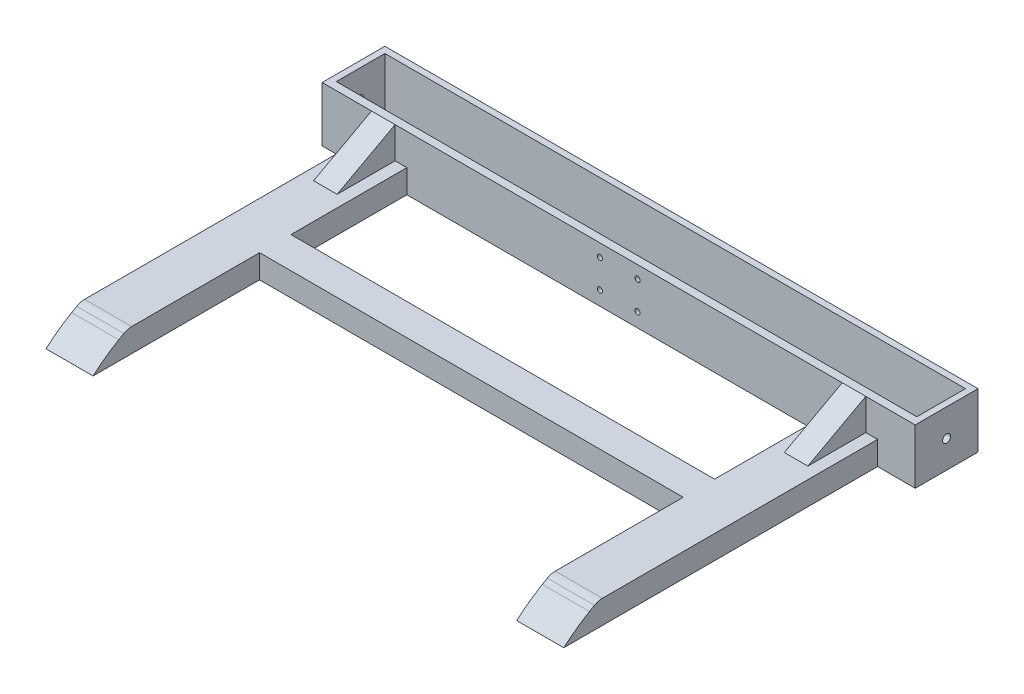
SolidWorks part; units mm, degrees
ref_plane "前视基准面" through (0, 0, 0) normal (0, 0, 1) x (1, 0, 0)
ref_plane "上视基准面" through (0, 0, 0) normal (0, 1, 0) x (1, 0, 0)
ref_plane "右视基准面" through (0, 0, 0) normal (1, 0, 0) x (0, 0, -1)
other "Configuration Table"
sketch "草图1" plane through (0, 0, 0) normal (0, 0, 1) x (1, 0, 0)
  line L0 (0, 0) -> (100.5587, 0) construction
  line L1 (0, 0) -> (0, 57.8212) construction
  line L2 (-189, 0) -> (189, 0)
  line L3 (-189, 0) -> (-189, 35)
  line L4 (189, 0) -> (189, 35)
  line L5 (189, 35) -> (-189, 35)
  point P8 (0, 0)
  dimension "D1" = 35
  dimension "D2" = 378
extrude "凸台-拉伸1" add sketch "草图1" along normal mid plane 5
sketch "草图2" plane through (0, 0, 2.5) normal (0, 0, 1) x (1, 0, 0)
  line L0 (0, 0) -> (0, 77.459) construction
  line L1 (0, 0) -> (206.4807, 0) construction
  line L2 (-12, 27) -> (-12, 9) construction
  circle A0 centre (-12, 9) radius 2
  circle A1 centre (-12, 27) radius 2
  circle A2 centre (12, 9) radius 2
  circle A3 centre (12, 27) radius 2
  point P4 (-12, 9)
  point P7 (-12, 27)
  point P9 (12, 9)
  point P11 (12, 27)
  dimension "D3" = 4
  dimension "D1" = 18
  dimension "D2" = 12
  dimension "D4" = 9
sketch "草图3" plane through (0, 0, -2.5) normal (0, 0, -1) x (-1, 0, 0)
  line L0 (0, 0) -> (0, 97.3013) construction
  line L1 (0, 0) -> (194.0159, 0) construction
  line L2 (-185, 0) -> (-185, 35)
  line L3 (-189, 35) -> (189, 35) construction
  line L4 (-189, 0) -> (-189, 35) construction
  line L5 (-189, 0) -> (-189, 35)
  line L6 (-189, 35) -> (-185, 35)
  line L8 (-189, 0) -> (-185, 0)
  line L9 (189, 0) -> (185, 0)
  line L10 (189, 35) -> (185, 35)
  line L11 (189, 0) -> (189, 35)
  line L12 (185, 0) -> (185, 35)
  dimension "D1" = 4
extrude "凸台-拉伸2" add sketch "草图3" along normal blind 35
sketch "草图4" plane through (189, 0, 0) normal (1, 0, 0) x (0, 0, -1)
  line L0 (-5, 17.5) -> (35, 17.5) construction
  line L3 (17.5, 17.5) -> (17.5, 35) construction
  line L5 (-2.5, 0) -> (37.5, 0) construction
  line L8 (-2.5, -200000) -> (-2.5, 200077.459) construction
  circle A0 centre (17.5, 17.5) radius 2.55
  point P3 (17.5, 0)
  dimension "D1" = 5.1
  dimension "D2" = 20
extrude "切除-拉伸3" cut sketch "草图4" against normal through all
hole_wizard "M4 螺纹孔的螺纹孔钻头6" positions "草图2" profile "草图5" hole size "M4" standard "GB" end condition up to next
sketch "草图5" plane through (12, 27, 2.5) normal (1, 0, 0) x (0, -1, 0)
  line L0 (0, 0) -> (0, 5)
  line L1 (0, 5) -> (1.65, 5)
  line L2 (1.65, 5) -> (1.65, 0)
  line L5 (1.65, 0) -> (0, 0)
  line L11 (0, -6.35) -> (0, 107.95) construction
  dimension "通孔孔直径" = 3.3
  dimension "通孔孔深度" = 5
sketch "草图6" plane through (0, 0, 2.5) normal (0, 0, 1) x (1, 0, 0)
  line L0 (0, 0) -> (0, 81.9275) construction
  line L2 (0, 0) -> (221.9261, 0) construction
  line L3 (-135, 15) -> (-135, 0)
  line L4 (135, 15) -> (165, 15)
  line L5 (135, 15) -> (135, 0)
  line L6 (135, 0) -> (165, 0)
  line L7 (165, 15) -> (165, 0)
  line L8 (135, 15) -> (165, 0) construction
  line L9 (135, 0) -> (165, 15) construction
  line L10 (-135, 15) -> (-165, 15)
  line L11 (-135, 0) -> (-165, 0)
  line L12 (-165, 15) -> (-165, 0)
  point P2 (150, 7.5)
  dimension "D1" = 30
  dimension "D2" = 15
  dimension "D3" = 7.5
  dimension "D4" = 150
extrude "凸台-拉伸3" add sketch "草图6" along normal blind 200
sketch "草图15" plane through (-135, 0, 0) normal (1, 0, 0) x (0, 0, -1)
  line L0 (-224.1671, 10) -> (50.3788, 10) construction
  line L2 (-86.3824, 25) -> (-86.3824, -41.1178) construction
  line L4 (-96.3824, 15) -> (-76.3824, 15)
  line L5 (-96.3824, 15) -> (-96.3824, 0)
  line L6 (-76.3824, 15) -> (-76.3824, 0)
  line L7 (-96.3824, 0) -> (-76.3824, 0)
  line L9 (-202.5, 15) -> (-2.5, 15) construction
  point P10 (-86.3824, 15)
  dimension "D1" = 15
  dimension "D2" = 20
extrude "凸台-拉伸4" add sketch "草图15" along normal up to next
sketch "草图17" plane through (185, 0, 0) normal (-1, 0, 0) x (0, 0, 1)
  line L0 (-33.5, 0) -> (-33.5, 35)
  line L1 (-37.5, 0) -> (-2.5, 0) construction
  line L2 (-37.5, 35) -> (-2.5, 35) construction
  line L3 (-37.5, 35) -> (-33.5, 35)
  line L4 (-37.5, 0) -> (-33.5, 0)
  line L5 (-37.5, 0) -> (-37.5, 35)
  dimension "D1" = 4
extrude "凸台-拉伸5" add sketch "草图17" along normal up to next
sketch "草图18" plane through (-185, 0, 0) normal (1, 0, 0) x (0, 0, -1)
  line L0 (33.5, 0) -> (33.5, 35)
  line L1 (-2.5, 0) -> (37.5, 0) construction
  line L2 (-2.5, 35) -> (37.5, 35) construction
  line L3 (33.5, 35) -> (37.5, 35)
  line L4 (37.5, 35) -> (37.5, 0)
  line L5 (37.5, 0) -> (33.5, 0)
  dimension "D1" = 4
extrude "凸台-拉伸6" add sketch "草图18" along normal blind 185
sketch "草图19" plane through (-165, 0, 0) normal (-1, 0, 0) x (0, 0, 1)
  line L0 (180.5936, 15) -> (202.5, 2.3523)
  line L1 (202.5, 15) -> (2.5, 15) construction
  line L2 (202.5, 15) -> (202.5, 0) construction
  line L3 (202.5, 2.3523) -> (158.0045, 2.3523) construction
  dimension "D1" = 30
extrude "切除-拉伸4" cut sketch "草图19" against normal through all and the other way through all
fillet "圆角1" radius 100 2 edges at (-150, 2.3523, 202.5) (150, 2.3523, 202.5)
fillet "圆角2" radius 10 2 edges at (-150, 15, 180.5936) (150, 15, 180.5936)
ref_plane "基准面1" through (150, 0, 0) normal (1, 0, 0) x (0, 0, -1)
sketch "草图20" plane through (150, 0, 0) normal (1, 0, 0) x (0, 0, -1)
  line L0 (-2.5, 35) -> (-39.4412, 15)
  line L2 (-76.3824, 15) -> (-2.5, 15) construction
rib "筋6" sketch "草图20" sketch "草图20" thickness 15 extrusion direction parallel to sketch draft on no parameters "D1"=15
mirror "镜向1" about plane through (0, 0, 0) normal (1, 0, 0) of "筋6"
